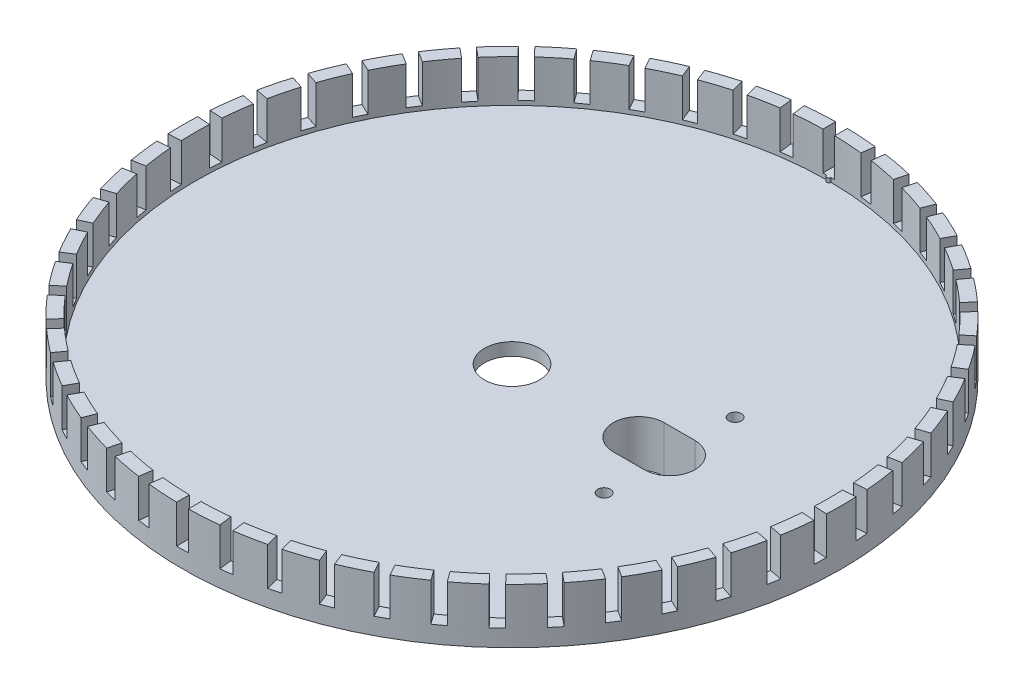
SolidWorks part; units mm, degrees
ref_plane "前视基准面" through (0, 0, 0) normal (0, 0, 1) x (1, 0, 0)
ref_plane "上视基准面" through (0, 0, 0) normal (0, 1, 0) x (1, 0, 0)
ref_plane "右视基准面" through (0, 0, 0) normal (1, 0, 0) x (0, 0, -1)
other "Configuration Table"
sketch "草图1" plane through (0, 0, 0) normal (0, 0, 1) x (1, 0, 0)
  line L0 (0, -268.4378) -> (0, 13153.4543) construction
  line L1 (0, 0) -> (-78, 0)
  line L2 (-78, 0) -> (-78, 13)
  line L3 (-78, 13) -> (-75, 13)
  line L4 (-75, 13) -> (-75, 3)
  line L5 (-75, 3) -> (0, 3)
  line L6 (0, 3) -> (0, 0)
  dimension "D1" = 10
  dimension "D2" = 3
  dimension "D3" = 156
  dimension "D4" = 3
revolve "旋转1" add sketch "草图1" angle 360 about L0
sketch "草图2" plane through (0, 0, 0) normal (0, 0, 1) x (1, 0, 0)
  line L0 (75, 13) -> (-75, 13) construction
  line L1 (-1.3827, 22) -> (1.3827, 22)
  line L2 (-1.3827, 22) -> (-1.3827, 4)
  line L3 (-1.3827, 4) -> (1.3827, 4)
  line L4 (1.3827, 22) -> (1.3827, 4)
  line L5 (-1.3827, 22) -> (1.3827, 4) construction
  line L6 (-1.3827, 4) -> (1.3827, 22) construction
  line L7 (-78, 0) -> (78, 0) construction
  point P0 (0, 13)
  dimension "D1" = 4
extrude "切除-拉伸1" cut sketch "草图2" against normal through all both and the other way through all
pattern_circular "阵列(圆周)1" count 50 over 360 about axis through (0, 13, 0) along (0, -1, 0) of "切除-拉伸1"
sketch "草图3" plane through (0, 13, 0) normal (0, 1, 0) x (1, 0, 0)
  circle A0 centre (0, 0) radius 75 construction
  circle A1 centre (0, 75) radius 0.5
  dimension "D1" = 150
  dimension "D2" = 1
extrude "凸台-拉伸1" add sketch "草图3" along normal blind 1 from offset 10 offset against normal yes
sketch "草图4" plane through (0, 3, 0) normal (0, 1, 0) x (1, 0, 0)
  circle A0 centre (0, 0) radius 6.5
  dimension "D1" = 13
extrude "切除-拉伸2" cut sketch "草图4" against normal through all both and the other way through all
sketch "草图5" plane through (0, 3, 0) normal (0, 1, 0) x (1, 0, 0)
  line L0 (-1000, 0) -> (49000, 0) construction
  line L1 (30, -1000) -> (30, 49000) construction
  line L2 (30, 0) -> (37.3, 0) construction
  line L3 (30, 6) -> (37.3, 6)
  line L4 (30, -6) -> (37.3, -6)
  line L5 (37.3, -1000) -> (37.3, 49000) construction
  arc A0 (30, 6) -> (30, -6) centre (30, 0) ccw
  arc A1 (37.3, -6) -> (37.3, 6) centre (37.3, 0) ccw
  circle A2 centre (37.3, 0) radius 15.5 construction
  circle A3 centre (37.3, 15.5) radius 1.5
  circle A4 centre (37.3, -15.5) radius 1.5
  point P7 (33.65, 0)
  dimension "D2" = 6
  dimension "D4" = 31
  dimension "D5" = 3
  dimension "D1" = 30
  dimension "D3" = 7.3
extrude "切除-拉伸3" cut sketch "草图5" against normal through all both and the other way through all
sketch "草图6" plane through (0, 0, 0) normal (0, -1, 0) x (1, 0, 0)
  circle A0 centre (37.3, 0) radius 20
  dimension "D1" = 40
extrude "凸台-拉伸2" add sketch "草图6" along normal blind 8
sketch "草图7" plane through (0, 0, 0) normal (0, 1, 0) x (1, 0, 0)
  line L2 (37.3, 6) -> (30, 6)
  line L3 (30, -6) -> (37.3, -6)
  line L4 (37.3, 6) -> (30, 6)
  line L5 (30, -6) -> (37.3, -6)
  circle A0 centre (37.3, -15.5) radius 1.5 construction
  circle A1 centre (37.3, 15.5) radius 1.5 construction
  arc A2 (30, 6) -> (30, -6) centre (30, 0) ccw
  arc A3 (37.3, -6) -> (37.3, 6) centre (37.3, 0) ccw
  arc A4 (30, 6) -> (30, -6) centre (30, 0) ccw
  arc A5 (37.3, -6) -> (37.3, 6) centre (37.3, 0) ccw
  circle A6 centre (37.3, -15.5) radius 1.5
  circle A7 centre (37.3, 15.5) radius 1.5
  dimension "D1" = 0
extrude "切除-拉伸4" cut sketch "草图7" against normal through all both and the other way through all
